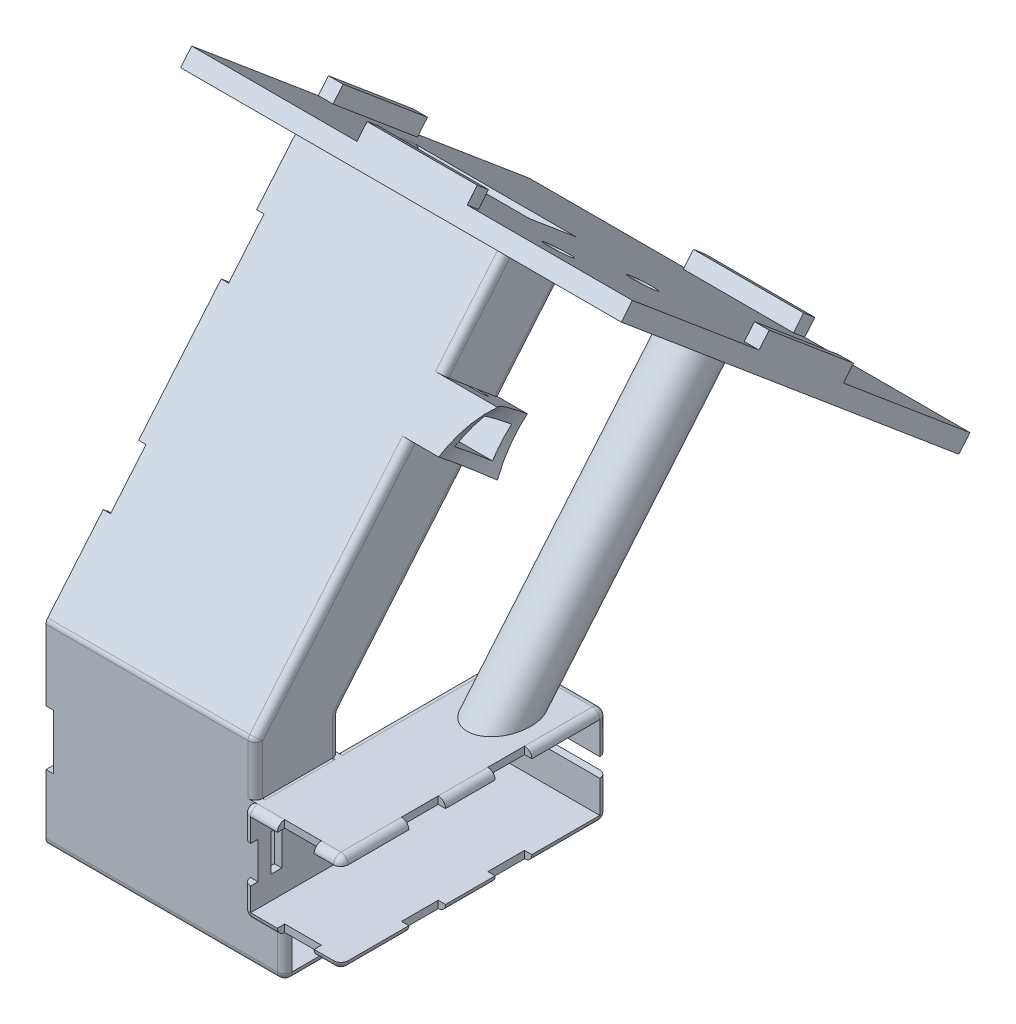
SolidWorks part; units mm, degrees
note: The reader was unsure of these and kept them because the rebuilt part matched: shared geometry of "Sketch1<7>", "Sketch30<3>".
material "ABS"
ref_plane "Front Plane" through (0, 0, 0) normal (0, 0, 1) x (1, 0, 0)
ref_plane "Top Plane" through (0, 0, 0) normal (0, 1, 0) x (1, 0, 0)
ref_plane "Right Plane" through (0, 0, 0) normal (1, 0, 0) x (0, 0, -1)
sketch "Sketch1" plane through (0, 0, 0) normal (0, 0, 1) x (1, 0, 0)
  line L1 (-12.3, -11.3) -> (12.3, -11.3)
  line L2 (-12.3, -11.3) -> (-12.3, 11.3)
  line L3 (-12.3, 11.3) -> (12.3, 11.3)
  line L4 (12.3, -11.3) -> (12.3, 11.3)
  line L5 (-12.3, -11.3) -> (12.3, 11.3) construction
  line L6 (-12.3, 11.3) -> (12.3, -11.3) construction
  line L11 (12.3, -13.3) -> (-14.3, -13.3)
  line L12 (12.3, -13.3) -> (12.3, 13.3)
  line L13 (12.3, 13.3) -> (-14.3, 13.3)
  line L14 (-14.3, -13.3) -> (-14.3, 13.3)
  point P0 (0, 0)
  point P11 (0, 11.3)
  dimension "D1" = 24.6
  dimension "D2" = 22.6
  dimension "D3" = 2
  dimension "D4" = 2
  dimension "D5" = 2
extrude "Boss-Extrude3" add sketch "Sketch1" along normal blind 2 contours L1 L4 L3 L2 | L14 L11 L12 L1 L2 L3 L13
extrude "Boss-Extrude4" add sketch "Sketch1<7>" along normal blind 72.5 contours L14 L11 L12 L1 L2 L3 L13
sketch "Sketch1<7>" plane through (0, 0, 0) normal (0, 0, 1) x (1, 0, 0) same geometry as "Sketch1"
sketch "Sketch2" plane through (0, 0, 0) normal (0, 0, -1) x (-1, 0, 0)
  line L0 (12.3, 11.3) -> (12.3, -11.3) construction
  line L1 (12.3, 11.3) -> (12.3, -11.3) construction
  line L2 (-12.3, -13.3) -> (-12.3, 13.3) construction
  line L3 (-12.3, -2.55) -> (1.95, -2.55)
  line L4 (-12.3, -2.55) -> (-12.3, 2.55)
  line L5 (-12.3, 2.55) -> (1.95, 2.55)
  line L6 (1.95, -2.55) -> (1.95, 2.55)
  line L7 (-12.3, -2.55) -> (1.95, 2.55) construction
  line L8 (-12.3, 2.55) -> (1.95, -2.55) construction
  point P2 (-5.175, 0)
  dimension "D1" = 5.1
  dimension "D2" = 10.35
extrude "Cut-Extrude1" cut sketch "Sketch2" against normal up to surface (2 mm away) up to face at (0, 0, 2)
sketch "Sketch3" plane through (-12.3, 0, 0) normal (1, 0, 0) x (0, 0, -1)
  line L0 (-2, 11.3) -> (-2, -11.3) construction
  line L1 (-72.5, -13.3) -> (-72.5, 13.3) construction
  line L2 (-67, 5) -> (-64, 5)
  line L3 (-67, 5) -> (-67, -5)
  line L4 (-67, -5) -> (-64, -5)
  line L5 (-64, 5) -> (-64, -5)
  line L6 (-67, 5) -> (-64, -5) construction
  line L7 (-67, -5) -> (-64, 5) construction
  circle A0 centre (-13.2, 0) radius 3
  point P2 (-65.5, 0)
  dimension "D2" = 6
  dimension "D1" = 11.2
  dimension "D3" = 3
  dimension "D4" = 10
  dimension "D5" = 7
extrude "Cut-Extrude2" cut sketch "Sketch3" against normal up to surface (2 mm away) up to face at (-14.3, 0, 36.25)
fillet "Fillet1" radius 2 5 edges at (-14.3, -13.3, 36.25) (-14.3, 13.3, 36.25) (-1, 13.3, 0) (-1, -13.3, 0) (-14.3, 0, 0)
sketch "Sketch4" plane through (0, 0, 72.5) normal (0, 0, 1) x (1, 0, 0)
  line L0 (-12.3, -11.3) -> (12.3, -11.3) construction
  line L1 (-5, -13.3) -> (5, -13.3)
  line L2 (-5, -13.3) -> (-5, -11.3)
  line L3 (-5, -11.3) -> (5, -11.3)
  line L4 (5, -13.3) -> (5, -11.3)
  line L5 (-5, -13.3) -> (5, -11.3) construction
  line L6 (-5, -11.3) -> (5, -13.3) construction
  line L7 (12.3, -13.3) -> (-12.3, -13.3) construction
  line L8 (0, 0) -> (-14.3, 0) construction
  line L9 (-14.3, -11.3) -> (-14.3, 11.3) construction
  line L10 (-5, 11.3) -> (5, 13.3) construction
  line L11 (-5, 13.3) -> (5, 11.3) construction
  line L12 (5, 13.3) -> (5, 11.3)
  line L13 (-5, 11.3) -> (5, 11.3)
  line L14 (-5, 13.3) -> (-5, 11.3)
  line L15 (-5, 13.3) -> (5, 13.3)
  line L16 (-12.3, 11.3) -> (-12.3, -11.3) construction
  line L17 (-14.3, -5) -> (-12.3, -5)
  line L18 (-14.3, -5) -> (-14.3, 5)
  line L19 (-14.3, 5) -> (-12.3, 5)
  line L20 (-12.3, -5) -> (-12.3, 5)
  line L21 (-14.3, -5) -> (-12.3, 5) construction
  line L22 (-14.3, 5) -> (-12.3, -5) construction
  point P0 (0, -12.3)
  point P18 (0, 12.3)
  point P19 (-13.3, 0)
  dimension "D1" = 10
  dimension "D2" = 10
extrude "Cut-Extrude3" cut sketch "Sketch4" against normal blind 2
sketch "Sketch5" plane through (12.3, 0, 0) normal (1, 0, 0) x (0, 0, -1)
  line L0 (-72.5, 13.3) -> (-2, 13.3) construction
  line L1 (-30.5, 11.3) -> (-20.5, 11.3)
  line L2 (-30.5, 11.3) -> (-30.5, 13.3)
  line L3 (-30.5, 13.3) -> (-20.5, 13.3)
  line L4 (-20.5, 11.3) -> (-20.5, 13.3)
  line L5 (-30.5, 11.3) -> (-20.5, 13.3) construction
  line L6 (-30.5, 13.3) -> (-20.5, 11.3) construction
  line L7 (-72.5, 11.3) -> (-2, 11.3) construction
  line L10 (-54, 11.3) -> (-44, 11.3)
  line L11 (-54, 11.3) -> (-54, 13.3)
  line L12 (-54, 13.3) -> (-44, 13.3)
  line L13 (-44, 11.3) -> (-44, 13.3)
  line L14 (-54, 11.3) -> (-44, 13.3) construction
  line L15 (-54, 13.3) -> (-44, 11.3) construction
  line L17 (-2, 11.3) -> (-2, -11.3) construction
  line L18 (-72.5, 11.3) -> (-72.5, 13.3) construction
  line L19 (0, 0) -> (-70.5, 0) construction
  line L20 (-70.5, -5) -> (-70.5, 5) construction
  line L21 (-54, -13.3) -> (-44, -11.3) construction
  line L22 (-54, -11.3) -> (-44, -13.3) construction
  line L23 (-30.5, -13.3) -> (-20.5, -11.3) construction
  line L24 (-30.5, -11.3) -> (-20.5, -13.3) construction
  line L25 (-44, -11.3) -> (-44, -13.3)
  line L26 (-54, -13.3) -> (-44, -13.3)
  line L27 (-54, -11.3) -> (-54, -13.3)
  line L28 (-54, -11.3) -> (-44, -11.3)
  line L29 (-20.5, -11.3) -> (-20.5, -13.3)
  line L30 (-30.5, -13.3) -> (-20.5, -13.3)
  line L31 (-30.5, -11.3) -> (-30.5, -13.3)
  line L32 (-30.5, -11.3) -> (-20.5, -11.3)
  point P0 (-25.5, 12.3)
  point P14 (-49, 12.3)
  point P31 (-49, -12.3)
  point P32 (-25.5, -12.3)
  dimension "D1" = 10
  dimension "D2" = 23.5
  dimension "D3" = 10
  dimension "D4" = 23.5
extrude "Cut-Extrude4" cut sketch "Sketch5" against normal blind 2
fillet "Fillet2" radius 2 18 edges at (-8.65, -13.3, 72.5) (-13.7142, -12.7142, 72.5) (-14.3, 8.15, 72.5) (-13.7142, 12.7142, 72.5) (12.3, 13.3, 11.25) (12.3, 12.7142, 0.5858) (12.3, -6.925, 0) (12.3, -12.7142, 0.5858) (8.65, -13.3, 72.5) (-14.3, -8.15, 72.5) (-8.65, 13.3, 72.5) (8.65, 13.3, 72.5) (12.3, 13.3, 63.25) (12.3, 13.3, 37.25) (12.3, 6.925, 0) (12.3, -13.3, 11.25) (12.3, -13.3, 37.25) (12.3, -13.3, 63.25)
ref_plane "Plane2" through (0, -7.6159, 6.3905) normal (0, 0.766, -0.6428) x (-1, 0, 0)
sketch "Sketch14" plane through (0, -7.6159, 6.3905) normal (0, 0.766, -0.6428) x (-1, 0, 0)
  line L0 (-10.3, 10.0812) -> (12.3, 10.0812) construction
  line L1 (12.3, 62.5552) -> (5, 62.5552) construction
  line L6 (12.3, 10.0812) -> (12.3, 62.5552) construction
  line L9 (6.3, 61.5552) -> (11.3, 61.5552)
  line L10 (6.3, 61.5552) -> (6.3, 46.5552)
  line L11 (6.3, 46.5552) -> (11.3, 46.5552)
  line L12 (11.3, 61.5552) -> (11.3, 46.5552)
  circle A0 centre (1, 20.0812) radius 7.5
  circle A1 centre (1, 20.0812) radius 5
  dimension "D1" = 15
  dimension "D2" = 5
  dimension "D3" = 15
  dimension "D4" = 10
  dimension "D5" = 11.3
  dimension "D7" = 1
  dimension "D8" = 1
  dimension "D6" = 2.5
extrude "Boss-Extrude10" add sketch "Sketch14" along normal blind 95 and the other way blind 33 contours A0 A1
ref_plane "Plane3" through (0, 0, 72.5) normal (0, 0, 1) x (1, 0, 0)
sketch "Sketch17" plane through (0, 0, 72.5) normal (0, 0, 1) x (1, 0, 0)
  line L1 (12.3, 11.3) -> (-12.3, 11.3)
  line L2 (12.3, 11.3) -> (12.3, -11.3)
  line L3 (12.3, -11.3) -> (-12.3, -11.3)
  line L4 (-12.3, 11.3) -> (-12.3, -11.3)
  line L5 (-12.3, -13.3) -> (12.3, -13.3)
  line L6 (-12.3, -13.3) -> (-12.3, -63.3)
  line L7 (-12.3, -63.3) -> (12.3, -63.3)
  line L8 (12.3, -13.3) -> (12.3, -63.3)
  dimension "D1" = 50
extrude "Cut-Extrude7" cut sketch "Sketch17" against normal blind 70 and the other way blind 56.7
sketch "Sketch18" plane through (0, 65.1583, -54.6743) normal (0, 0.766, -0.6428) x (-1, 0, 0)
  line L1 (-47.7, -7.4448) -> (72.3, -7.4448)
  line L2 (-47.7, -7.4448) -> (-47.7, 112.5552)
  line L3 (-47.7, 112.5552) -> (72.3, 112.5552)
  line L4 (72.3, -7.4448) -> (72.3, 112.5552)
  line L5 (-5, 62.5552) -> (5, 62.5552) construction
  line L7 (12.3, 10.0812) -> (12.3, 62.5552) construction
  dimension "D1" = 50
  dimension "D2" = 60
  dimension "D3" = 120
  dimension "D4" = 120
extrude "Boss-Extrude11" add sketch "Sketch18" along normal blind 4.7
sketch "Sketch21" plane through (0, 65.1583, -54.6743) normal (0, -0.766, 0.6428) x (1, 0, 0)
  line L0 (10.1, 9.1618) -> (18, 9.1618) construction
  line L1 (-72.3, 112.5552) -> (47.7, 112.5552) construction
  line L2 (18, 7.4393) -> (18, 10.1971) construction
  circle A0 centre (16, 67.5552) radius 3.55
  circle A1 centre (16, 97.5552) radius 3.55
  point P10 (16, 9.1618)
  dimension "D1" = 7.1
  dimension "D2" = 7.1
  dimension "D3" = 15
  dimension "D4" = 30
  dimension "D5" = 2
extrude "Cut-Extrude8" cut sketch "Sketch21" against normal up to surface (4.7 mm away) up to face at (-12.3, 102.5405, -17.4358)
ref_plane "Plane5" through (-6, 112.1824, -5.9451) normal (-1, 0, 0) x (0, -0.766, 0.6428)
sketch "Sketch22" plane through (-6, 112.1824, -5.9451) normal (-1, 0, 0) x (0, -0.766, 0.6428)
  line L0 (48.4938, 4.1919) -> (48.4938, -16.3081)
  line L1 (45.4938, 1.1919) -> (37.4938, 1.1919)
  line L2 (45.4938, 1.1919) -> (45.4938, -13.3081)
  line L3 (45.4938, -13.3081) -> (37.4938, -13.3081)
  line L4 (37.4938, 1.1919) -> (37.4938, -13.3081)
  line L5 (48.4938, -16.3081) -> (34.4938, -16.3081)
  line L6 (34.4938, 4.1919) -> (34.4938, -16.3081)
  line L7 (48.4938, 4.1919) -> (34.4938, 4.1919)
  dimension "D1" = 3
extrude "Boss-Extrude12" add sketch "Sketch22" along normal blind 53 and the other way up to surface separate body
sketch "Sketch29" plane through (-5, 0, 0) normal (1, 0, 0) x (0, 0, -1)
  line L0 (-70.5, -13.3) -> (-70.5, -25.6)
  line L1 (-70.5, -25.6) -> (-47.5, -25.6)
  line L2 (-47.5, -25.6) -> (-47.5, -13.3)
  line L3 (-70.5, -13.3) -> (-2, -13.3) construction
  line L4 (-47.5, -13.3) -> (-49.5, -13.3)
  line L5 (-49.5, -13.3) -> (-49.5, -23.6)
  line L6 (-49.5, -23.6) -> (-68.5, -23.6)
  line L7 (-68.5, -23.6) -> (-68.5, -13.3)
  line L8 (-70.5, -13.3) -> (-68.5, -13.3)
  dimension "D1" = 2
  dimension "D2" = 2
  dimension "D3" = 2
  dimension "D4" = 10.3
  dimension "D5" = 19
extrude "Boss-Extrude16" add sketch "Sketch29" against normal blind 65 contours L8 L0 L1 L2 L4 L5 L6 L7
sketch "Sketch30" plane through (0, -13.3, 0) normal (0, 1, 0) x (1, 0, 0)
  line L1 (-12.3, -68.5) -> (-70, -68.5) construction
  line L3 (-70, -70.5) -> (-12.3, -70.5) construction
  line L5 (-12.3, -47.5) -> (-70, -47.5) construction
  line L7 (-70, -49.5) -> (-12.3, -49.5) construction
  line L9 (-12.3, -68.5) -> (-70, -68.5)
  line L11 (-70, -70.5) -> (-12.3, -70.5)
  line L13 (-12.3, -47.5) -> (-70, -47.5)
  line L15 (-70, -49.5) -> (-12.3, -49.5)
  line L16 (-12.3, -47.5) -> (-12.3, -49.5)
  line L18 (-12.3, -70.5) -> (-12.3, -68.5)
  line L19 (-70, -47.5) -> (-70, -49.5)
  line L20 (-70, -68.5) -> (-70, -70.5)
extrude "Boss-Extrude17" add sketch "Sketch30" along normal up to surface (36.418 mm away)
extrude "Boss-Extrude18" add sketch "Sketch30<3>" along normal up to surface (40.9 mm away)
sketch "Sketch30<3>" plane through (0, -13.3, 0) normal (0, 1, 0) x (1, 0, 0) same geometry as "Sketch30"
sketch "Sketch34" plane through (-70, 0, 0) normal (-1, 0, 0) x (0, 0, 1)
  line L1 (49.5, 20.7345) -> (-15.4168, 98.0993)
  line L2 (-60.3773, 60.3729) -> (31.548, 137.5074) construction
  line L3 (70.5, 27.6) -> (68.9679, 26.3145)
  line L4 (68.9679, 26.3145) -> (-1.2449, 109.9909)
  line L5 (-1.2449, 109.9909) -> (0.2872, 111.2764)
  line L7 (49.5, 23.846) -> (-13.8847, 99.3849)
  line L8 (-13.8847, 99.3849) -> (-15.4168, 98.0993)
  line L9 (49.5, 23.846) -> (49.5, 20.7345)
  line L10 (70.5, 27.6) -> (70.5, -25.6) construction
  line L11 (70.5, 27.6) -> (68.5, 29.9835) construction
  line L12 (0.2872, 111.2764) -> (70.5, 27.6)
  line L13 (49.5, 20.7345) -> (49.5, -23.6) construction
  line L14 (47.5, 23.118) -> (49.5, 20.7345) construction
  dimension "D1" = 2
  dimension "D2" = 2
extrude "Boss-Extrude19" add sketch "Sketch34" against normal blind 57
sketch "Sketch36" plane through (0, 0, 70.5) normal (0, 0, 1) x (1, 0, 0)
  line L1 (-12.3, 11.3) -> (12.3, 11.3)
  line L2 (-12.3, 11.3) -> (-12.3, -11.3)
  line L3 (-12.3, -11.3) -> (12.3, -11.3)
  line L4 (12.3, 11.3) -> (12.3, -11.3)
  line L5 (-13, 29.9835) -> (10.3, 29.9835)
  line L6 (-13, 29.9835) -> (-13, 13.3)
  line L7 (-13, 13.3) -> (10.3, 13.3)
  line L8 (10.3, 29.9835) -> (10.3, 13.3)
  line M8 (5, 13.3) -> (-5, 13.3)
extrude "Cut-Extrude12" cut sketch "Sketch36" against normal blind 31 contours L8 L5 L6 L7 M8
sketch "Sketch37" plane through (0, 31.6103, -26.5242) normal (0, -0.766, 0.6428) x (1, 0, 0)
  circle A4 centre (-39.1164, 61.6471) radius 3.5
  arc A6 (-39.1164, 63.1471) -> (-39.1164, 60.1471) centre (-39.1164, 61.6471) ccw construction
  dimension "D1" = 7
extrude "Cut-Extrude14" cut sketch "Sketch37" against normal up to surface (3 mm away) contours A4 up to face at (-32.3337, 73.4489, 18.6699)
sketch "Sketch38" plane through (0, 40.0368, -33.5949) normal (0, -0.766, 0.6428) x (1, 0, 0)
  line L0 (-10.1243, 63.1471) -> (-39.1164, 63.1471)
  line L1 (-10.1243, 60.1471) -> (-39.1164, 60.1471)
  line L2 (-39.1164, 63.1471) -> (-50.1243, 63.1471)
  line L3 (-39.1164, 60.1471) -> (-50.1243, 60.1471)
  arc A0 (-10.1243, 60.1471) -> (-10.1243, 63.1471) centre (-10.1243, 61.6471) ccw
  arc A1 (-50.1243, 63.1471) -> (-50.1243, 60.1471) centre (-50.1243, 61.6471) ccw
  arc A2 (-39.1164, 63.1471) -> (-39.1164, 60.1471) centre (-39.1164, 61.6471) ccw construction
  arc A3 (-39.1164, 60.1471) -> (-39.1164, 63.1471) centre (-39.1164, 61.6471) ccw construction
  arc A5 (-39.1164, 60.1471) -> (-39.1164, 63.1471) centre (-39.1164, 61.6471) ccw construction
  dimension "D1" = 1.5
  dimension "D2" = 5
  dimension "D3" = 40
extrude "Cut-Extrude15" cut sketch "Sketch38" against normal up to surface (3 mm away) up to face at (-21.8729, 81.9488, 11.6867)
sketch "Sketch39" plane through (-13, 0, 0) normal (1, 0, 0) x (0, 0, -1)
  line L0 (-47.5, 13.3) -> (-47.5, 23.118) construction
  line L1 (-12.7333, 64.5513) -> (-47.5, 23.118) construction
  line L2 (15.4168, 98.0993) -> (-3.7343, 75.2759) construction
  line L3 (-19.4382, 88.4531) -> (-0.2872, 111.2764) construction
  line L4 (-70.5, 27.6) -> (-28.4373, 77.7285) construction
  line L5 (-70.5, 27.6) -> (-70.5, 13.3) construction
  line L6 (-47.5, 13.3) -> (-47.5, 23.118)
  line L7 (-12.7333, 64.5513) -> (-47.5, 23.118)
  line L8 (15.4168, 98.0993) -> (-3.7343, 75.2759)
  line L9 (-19.4382, 88.4531) -> (-0.2872, 111.2764)
  line L10 (-70.5, 27.6) -> (-28.4373, 77.7285)
  line L11 (-70.5, 27.6) -> (-70.5, 13.3)
  line L12 (-0.2872, 111.2764) -> (15.4168, 98.0993)
  line L13 (-3.7343, 75.2759) -> (-19.4382, 88.4531)
  line L14 (-28.4373, 77.7285) -> (-12.7333, 64.5513)
  line L15 (-47.5, 13.3) -> (-70.5, 13.3)
  line M11 (-68.5, 13.3) -> (-68.5, 26.8721)
  line M12 (-68.5, 26.8721) -> (-26.9052, 76.4429)
extrude "Boss-Extrude20" add sketch "Sketch39" against normal blind 2 contours L13 L8 L12 L9 | L15 L6 L7 L14 M12 M11
sketch "Sketch41" plane through (-70, 0, 0) normal (-1, 0, 0) x (0, 0, 1)
  line L0 (13.1429, 95.9556) -> (22.7847, 84.4649)
  line L1 (13.1429, 95.9556) -> (11.6108, 94.67)
  line L2 (22.7847, 84.4649) -> (21.2526, 83.1793)
  line L3 (11.6108, 94.67) -> (21.2526, 83.1793)
  line L4 (-60.3773, 60.3729) -> (31.548, 137.5074) construction
  line L5 (49.5, -7.377) -> (49.5, 7.623)
  line L6 (-1.2449, 109.9909) -> (17.9061, 87.1675) construction
  line L8 (45.2823, 57.6533) -> (54.9241, 46.1627)
  line L9 (45.2823, 57.6533) -> (43.7502, 56.3678)
  line L10 (54.9241, 46.1627) -> (53.392, 44.8771)
  line L11 (43.7502, 56.3678) -> (53.392, 44.8771)
  line L12 (-13.8847, 99.3849) -> (-1.2449, 109.9909) construction
  line L13 (-7.5648, 104.6879) -> (68.5, 14.0374) construction
  line L14 (49.5, -23.6) -> (68.5, -23.6) construction
  line L15 (31.1105, 45.7618) -> (40.7523, 34.2711)
  line L16 (39.2202, 32.9855) -> (40.7523, 34.2711)
  line L17 (29.5784, 44.4762) -> (31.1105, 45.7618)
  line L18 (29.5784, 44.4762) -> (39.2202, 32.9855)
  line L19 (-1.0289, 84.064) -> (8.6129, 72.5733)
  line L20 (7.0808, 71.2877) -> (8.6129, 72.5733)
  line L21 (-2.561, 82.7784) -> (-1.0289, 84.064)
  line L22 (-2.561, 82.7784) -> (7.0808, 71.2877)
  line L23 (49.5, 23.846) -> (49.5, -23.6) construction
  line L24 (70.5, -7.377) -> (68.5, -7.377)
  line L25 (70.5, -7.377) -> (70.5, 7.623)
  line L26 (70.5, 7.623) -> (68.5, 7.623)
  line L27 (68.5, -7.377) -> (68.5, 7.623)
  line L28 (68.5, 11.3) -> (68.5, -11.3) construction
  line L30 (54, -25.6) -> (64, -25.6)
  line L31 (54, -25.6) -> (54, -23.6)
  line L32 (54, -23.6) -> (64, -23.6)
  line L33 (64, -25.6) -> (64, -23.6)
  line L36 (59, -23.6) -> (59, 25.359) construction
  line L37 (47.5, 7.623) -> (49.5, 7.623)
  line L38 (47.5, -7.377) -> (47.5, 7.623)
  line L39 (47.5, -7.377) -> (49.5, -7.377)
  line L40 (70.5, -25.6) -> (47.5, -25.6) construction
  line L41 (70.5, -11.3) -> (70.5, -5) construction
  line L42 (68.5, -23.6) -> (68.5, 26.8721) construction
  line L43 (70.5, 27.6) -> (0.2872, 111.2764) construction
  line L46 (-60.3773, 60.3729) -> (31.548, 137.5074) construction
  point P16 (2.2599, 77.0331)
  point P20 (-7.5648, 104.6879)
  point P48 (59, -23.6)
  point P49 (59, -23.6)
  point P59 (34.3993, 38.7309)
  point P66 (49.5, 0.123)
  point P68 (68.5, 0.123)
  dimension "D1" = 15
  dimension "D2" = 20
  dimension "D4" = 35
  dimension "D5" = 10
  dimension "D6" = 15
  dimension "D7" = 27.5
  dimension "D8" = 50
  dimension "D3" = 2
extrude "Cut-Extrude16" cut sketch "Sketch41" against normal blind 2
sketch "Sketch42" plane through (0, 68.7587, -57.6954) normal (0, 0.766, -0.6428) x (1, 0, 0)
  line L0 (-15, -69.7471) -> (-70, -69.7471) construction
  line L1 (-15, -69.7471) -> (-55, -69.7471)
  line L2 (-15, -53.2471) -> (-70, -53.2471) construction
  line L3 (-15, -53.2471) -> (-55, -53.2471)
  line L4 (47.7, -112.5552) -> (47.7, 7.4448)
  line L5 (47.7, 7.4448) -> (-72.3, 7.4448)
  line L6 (-72.3, 7.4448) -> (-72.3, -112.5552)
  line L7 (-72.3, -112.5552) -> (47.7, -112.5552)
  line L8 (47.7, -112.5552) -> (47.7, 7.4448)
  line L9 (47.7, 7.4448) -> (-72.3, 7.4448)
  line L10 (-72.3, 7.4448) -> (-72.3, -112.5552)
  line L11 (-72.3, -112.5552) -> (47.7, -112.5552)
  line L12 (-15, -53.2471) -> (-15, -69.7471)
  line L13 (-55, -53.2471) -> (-55, -69.7471)
  dimension "D2" = 40
  dimension "D1" = 0
extrude "Cut-Extrude17" cut sketch "Sketch42" against normal up to surface (4.7 mm away) contours L3 L13 L1 L12 up to face at (-42, 104.6879, -7.5648)
fillet "Fillet3" radius 2 25 edges at (-41.5, 23.118, 47.5) (-13, 43.8347, 30.1167) (-13, 86.6876, -5.8412) (-41.5, 98.0993, -15.4168) (-37, 65.8369, 14.2654) (-41.5, 27.6, 70.5) (-13, 20.45, 70.5) (-13, 13.3, 69.5) (-13, 18.209, 47.5) (-13, 13.3, 48.5) (-37, 76.4429, 26.9052) (-55, 108.2883, -10.5859) (-55, 104.6879, -7.5648) (-15, 108.2883, -10.5859) (-13, 99.8648, 9.8627) (-41.5, 111.2764, 0.2872) (-13, 104.6879, -7.5648) (-13, 52.6642, 49.4686) (-5, -13.3, 69.5) (-37.5, -25.6, 70.5) (-37.5, -25.6, 47.5) (-5, -19.45, 70.5) (-5, -25.6, 59) (-5, -19.45, 47.5) (-5, -13.3, 48.5)
sketch "Sketch43" plane through (0, 68.7587, -57.6954) normal (0, 0.766, -0.6428) x (1, 0, 0)
  line L0 (47.7, 7.4448) -> (-72.3, 7.4448) construction
  line L1 (-27.3, 7.4448) -> (2.7, 7.4448)
  line L2 (-27.3, 7.4448) -> (-27.3, 3.4448)
  line L3 (-27.3, 3.4448) -> (2.7, 3.4448)
  line L4 (2.7, 7.4448) -> (2.7, 3.4448)
  line L5 (47.7, -112.5552) -> (47.7, 7.4448) construction
  line L6 (47.7, -37.5552) -> (43.7, -37.5552)
  line L7 (47.7, -37.5552) -> (47.7, -67.5552)
  line L8 (47.7, -67.5552) -> (43.7, -67.5552)
  line L9 (43.7, -37.5552) -> (43.7, -67.5552)
  line L10 (-72.3, -52.5552) -> (47.7, -52.5552) construction
  line L11 (-72.3, 7.4448) -> (-72.3, -112.5552) construction
  line L12 (-12.3, -112.5552) -> (-12.3, 7.4448) construction
  line L13 (-72.3, -112.5552) -> (47.7, -112.5552) construction
  line L14 (2.7, -112.5552) -> (2.7, -108.5552)
  line L15 (-27.3, -108.5552) -> (2.7, -108.5552)
  line L16 (-27.3, -112.5552) -> (-27.3, -108.5552)
  line L17 (-27.3, -112.5552) -> (2.7, -112.5552)
  line L18 (-68.3, -37.5552) -> (-68.3, -67.5552)
  line L19 (-72.3, -67.5552) -> (-68.3, -67.5552)
  line L20 (-72.3, -37.5552) -> (-72.3, -67.5552)
  line L21 (-72.3, -37.5552) -> (-68.3, -37.5552)
  point P20 (-12.3, 3.4448)
  point P21 (43.7, -52.5552)
  dimension "D1" = 4
  dimension "D2" = 30
  dimension "D3" = 30
  dimension "D4" = 4
extrude "Boss-Extrude21" add sketch "Sketch43" along normal blind 4.3
sketch "Sketch44" plane through (0, -25.6, 0) normal (0, -1, 0) x (1, 0, 0)
  line L0 (-13, 49.5) -> (-13, 68.5) construction
  circle A0 centre (-13, 52.4) radius 1.75
  circle A1 centre (-13.8554, 52.4) radius 1.75 construction
  point P2 (-13.8554, 52.4)
extrude "Cut-Extrude18" cut sketch "Sketch44" against normal up to surface (2 mm away) up to face at (-53.25, -23.6, 59)
